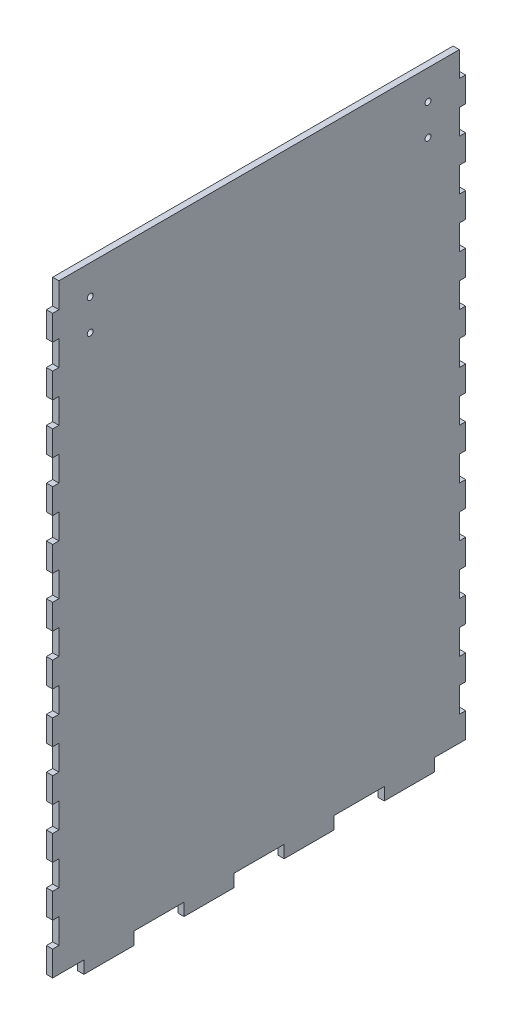
SolidWorks part; units mm, degrees
ref_plane "Front Plane" through (0, 0, 0) normal (0, 0, 1) x (1, 0, 0)
ref_plane "Top Plane" through (0, 0, 0) normal (0, 1, 0) x (1, 0, 0)
ref_plane "Right Plane" through (0, 0, 0) normal (1, 0, 0) x (0, 0, -1)
sketch "Sketch1" plane through (0, 0, 0) normal (1, 0, 0) x (0, 0, -1)
  line L0 (0, 0) -> (203.2, 0)
  line L1 (203.2, 0) -> (203.2, 304.8)
  line L2 (203.2, 304.8) -> (0, 304.8)
  line L3 (0, 304.8) -> (0, 0)
  line L4 (101.6, 304.8) -> (101.6, 0) construction
  line L5 (0, 0) -> (-3.175, 0)
  line L6 (-3.175, 0) -> (-3.175, 12.7)
  line L7 (-3.175, 12.7) -> (0, 12.7)
  line L8 (0, 12.7) -> (0, 0)
  line L9 (0, 25.4) -> (-3.175, 25.4)
  line L10 (-3.175, 25.4) -> (-3.175, 38.1)
  line L11 (-3.175, 38.1) -> (0, 38.1)
  line L12 (0, 38.1) -> (0, 25.4)
  line L13 (0, 50.8) -> (-3.175, 50.8)
  line L14 (-3.175, 50.8) -> (-3.175, 63.5)
  line L15 (-3.175, 63.5) -> (0, 63.5)
  line L16 (0, 63.5) -> (0, 50.8)
  line L17 (0, 76.2) -> (-3.175, 76.2)
  line L18 (-3.175, 76.2) -> (-3.175, 88.9)
  line L19 (-3.175, 88.9) -> (0, 88.9)
  line L20 (0, 88.9) -> (0, 76.2)
  line L21 (0, 101.6) -> (-3.175, 101.6)
  line L22 (-3.175, 101.6) -> (-3.175, 114.3)
  line L23 (-3.175, 114.3) -> (0, 114.3)
  line L24 (0, 114.3) -> (0, 101.6)
  line L25 (0, 127) -> (-3.175, 127)
  line L26 (-3.175, 127) -> (-3.175, 139.7)
  line L27 (-3.175, 139.7) -> (0, 139.7)
  line L28 (0, 139.7) -> (0, 127)
  line L29 (0, 152.4) -> (-3.175, 152.4)
  line L30 (-3.175, 152.4) -> (-3.175, 165.1)
  line L31 (-3.175, 165.1) -> (0, 165.1)
  line L32 (0, 165.1) -> (0, 152.4)
  line L33 (0, 177.8) -> (-3.175, 177.8)
  line L34 (-3.175, 177.8) -> (-3.175, 190.5)
  line L35 (-3.175, 190.5) -> (0, 190.5)
  line L36 (0, 190.5) -> (0, 177.8)
  line L37 (0, 203.2) -> (-3.175, 203.2)
  line L38 (-3.175, 203.2) -> (-3.175, 215.9)
  line L39 (-3.175, 215.9) -> (0, 215.9)
  line L40 (0, 215.9) -> (0, 203.2)
  line L41 (0, 228.6) -> (-3.175, 228.6)
  line L42 (-3.175, 228.6) -> (-3.175, 241.3)
  line L43 (-3.175, 241.3) -> (0, 241.3)
  line L44 (0, 241.3) -> (0, 228.6)
  line L45 (0, 254) -> (-3.175, 254)
  line L46 (-3.175, 254) -> (-3.175, 266.7)
  line L47 (-3.175, 266.7) -> (0, 266.7)
  line L48 (0, 266.7) -> (0, 254)
  line L49 (0, 279.4) -> (-3.175, 279.4)
  line L50 (-3.175, 279.4) -> (-3.175, 292.1)
  line L51 (-3.175, 292.1) -> (0, 292.1)
  line L52 (0, 292.1) -> (0, 279.4)
  line L53 (0, 0) -> (0, 25.4) construction
  line L54 (12.7, 0) -> (12.7, -6.35)
  line L55 (12.7, -6.35) -> (38.1, -6.35)
  line L56 (38.1, -6.35) -> (38.1, 0)
  line L57 (38.1, 0) -> (12.7, 0)
  line L58 (88.9, 0) -> (63.5, 0)
  line L59 (63.5, 0) -> (63.5, -6.35)
  line L60 (63.5, -6.35) -> (88.9, -6.35)
  line L61 (88.9, -6.35) -> (88.9, 0)
  line L62 (139.7, 0) -> (114.3, 0)
  line L63 (114.3, 0) -> (114.3, -6.35)
  line L64 (114.3, -6.35) -> (139.7, -6.35)
  line L65 (139.7, -6.35) -> (139.7, 0)
  line L66 (190.5, 0) -> (165.1, 0)
  line L67 (165.1, 0) -> (165.1, -6.35)
  line L68 (165.1, -6.35) -> (190.5, -6.35)
  line L69 (190.5, -6.35) -> (190.5, 0)
  line L70 (38.1, 0) -> (88.9, 0) construction
  line L71 (203.2, 12.7) -> (203.2, 0)
  line L72 (206.375, 12.7) -> (203.2, 12.7)
  line L73 (206.375, 0) -> (206.375, 12.7)
  line L74 (203.2, 0) -> (206.375, 0)
  line L75 (203.2, 38.1) -> (203.2, 25.4)
  line L76 (206.375, 38.1) -> (203.2, 38.1)
  line L77 (206.375, 25.4) -> (206.375, 38.1)
  line L78 (203.2, 25.4) -> (206.375, 25.4)
  line L79 (203.2, 63.5) -> (203.2, 50.8)
  line L80 (206.375, 63.5) -> (203.2, 63.5)
  line L81 (206.375, 50.8) -> (206.375, 63.5)
  line L82 (203.2, 50.8) -> (206.375, 50.8)
  line L83 (203.2, 88.9) -> (203.2, 76.2)
  line L84 (206.375, 88.9) -> (203.2, 88.9)
  line L85 (206.375, 76.2) -> (206.375, 88.9)
  line L86 (203.2, 76.2) -> (206.375, 76.2)
  line L87 (203.2, 114.3) -> (203.2, 101.6)
  line L88 (206.375, 114.3) -> (203.2, 114.3)
  line L89 (206.375, 101.6) -> (206.375, 114.3)
  line L90 (203.2, 101.6) -> (206.375, 101.6)
  line L91 (203.2, 139.7) -> (203.2, 127)
  line L92 (206.375, 139.7) -> (203.2, 139.7)
  line L93 (206.375, 127) -> (206.375, 139.7)
  line L94 (203.2, 127) -> (206.375, 127)
  line L95 (203.2, 165.1) -> (203.2, 152.4)
  line L96 (206.375, 165.1) -> (203.2, 165.1)
  line L97 (206.375, 152.4) -> (206.375, 165.1)
  line L98 (203.2, 152.4) -> (206.375, 152.4)
  line L99 (203.2, 190.5) -> (203.2, 177.8)
  line L100 (206.375, 190.5) -> (203.2, 190.5)
  line L101 (206.375, 177.8) -> (206.375, 190.5)
  line L102 (203.2, 177.8) -> (206.375, 177.8)
  line L103 (203.2, 215.9) -> (203.2, 203.2)
  line L104 (206.375, 215.9) -> (203.2, 215.9)
  line L105 (206.375, 203.2) -> (206.375, 215.9)
  line L106 (203.2, 203.2) -> (206.375, 203.2)
  line L107 (203.2, 241.3) -> (203.2, 228.6)
  line L108 (206.375, 241.3) -> (203.2, 241.3)
  line L109 (206.375, 228.6) -> (206.375, 241.3)
  line L110 (203.2, 228.6) -> (206.375, 228.6)
  line L111 (203.2, 266.7) -> (203.2, 254)
  line L112 (206.375, 266.7) -> (203.2, 266.7)
  line L113 (206.375, 254) -> (206.375, 266.7)
  line L114 (203.2, 254) -> (206.375, 254)
  line L115 (203.2, 292.1) -> (203.2, 279.4)
  line L116 (206.375, 292.1) -> (203.2, 292.1)
  line L117 (206.375, 279.4) -> (206.375, 292.1)
  line L118 (203.2, 279.4) -> (206.375, 279.4)
  dimension "D1" = 203.2
  dimension "D2" = 304.8
  dimension "D3" = 3.175
  dimension "D4" = 12.7
  dimension "D6" = 25.4
  dimension "D7" = 6.35
  dimension "D8" = 25.4
  dimension "D9" = 12.7
  dimension "D11" = 50.8
  dimension "D5" = 12
  dimension "D10" = 4
extrude "Boss-Extrude1" add sketch "Sketch1" along normal blind 3.175 contours L51 L50 L49 L3 | L47 L46 L45 L3 | L43 L42 L41 L3 | L39 L38 L37 L3 | L35 L34 L33 L3 | L31 L30 L29 L3 | L27 L26 L25 L3 | L23 L22 L21 L3 | L19 L18 L17 L3 | L15 L14 L13 L3 | L11 L10 L9 L3 | L2 L3 L0 L1 | L7 L6 L5 L3 | L55 L56 L0 L54 | L60 L61 L0 L59 | L64 L65 L0 L63 | L68 L69 L0 L67 | L1 L74 L73 L72 | L1 L78 L77 L76 | L1 L82 L81 L80 | L1 L86 L85 L84 | L1 L90 L89 L88 | L1 L94 L93 L92 | L1 L98 L97 L96 | L1 L102 L101 L100 | L1 L106 L105 L104 | L1 L110 L109 L108 | L1 L114 L113 L112 | L1 L118 L117 L116 region at (0, 152.4, -101.6) region at (0, 6.35, 1.5875) region at (0, -3.175, -25.4) region at (0, 31.75, 1.5875) region at (0, -3.175, -76.2) region at (0, 57.15, 1.5875) region at (0, -3.175, -127) region at (0, 82.55, 1.5875) region at (0, -3.175, -177.8) region at (0, 107.95, 1.5875) region at (0, 6.35, -204.7875) region at (0, 133.35, 1.5875) region at (0, 31.75, -204.7875) region at (0, 158.75, 1.5875) region at (0, 57.15, -204.7875) region at (0, 184.15, 1.5875) region at (0, 82.55, -204.7875) region at (0, 209.55, 1.5875) region at (0, 107.95, -204.7875) region at (0, 234.95, 1.5875) region at (0, 133.35, -204.7875) region at (0, 260.35, 1.5875) region at (0, 158.75, -204.7875) region at (0, 285.75, 1.5875) region at (0, 184.15, -204.7875) region at (0, 209.55, -204.7875) region at (0, 285.75, -204.7875) region at (0, 234.95, -204.7875) region at (0, 260.35, -204.7875)
sketch "Sketch2" plane through (3.175, 0, 0) normal (1, 0, 0) x (0, 0, -1)
  line L1 (203.2, 304.8) -> (0, 304.8) construction
  line L2 (101.6, 304.8) -> (101.6, 0) construction
  line L3 (88.9, 0) -> (114.3, 0) construction
  line L4 (-3.175, 279.4) -> (-3.175, 292.1) construction
  circle A0 centre (15.875, 289.8) radius 1.5
  circle A1 centre (15.875, 274.05) radius 1.5
  circle A2 centre (187.325, 274.05) radius 1.5
  circle A3 centre (187.325, 289.8) radius 1.5
  dimension "D1" = 3
  dimension "D2" = 3
  dimension "D3" = 19.05
  dimension "D4" = 15.75
  dimension "D5" = 15
extrude "Cut-Extrude1" cut sketch "Sketch2" against normal up to surface (3.175 mm away) up to face at (0, 130.175, -101.6)
equation "\"wall_thickness\"= 0.125in"
equation "\"base_thickness\"= 0.25in"
equation "\"D3@Sketch1\"=\"wall_thickness\""
equation "\"D7@Sketch1\"=\"base_thickness\""
equation "\"D1@Boss-Extrude1\"=\"wall_thickness\""
